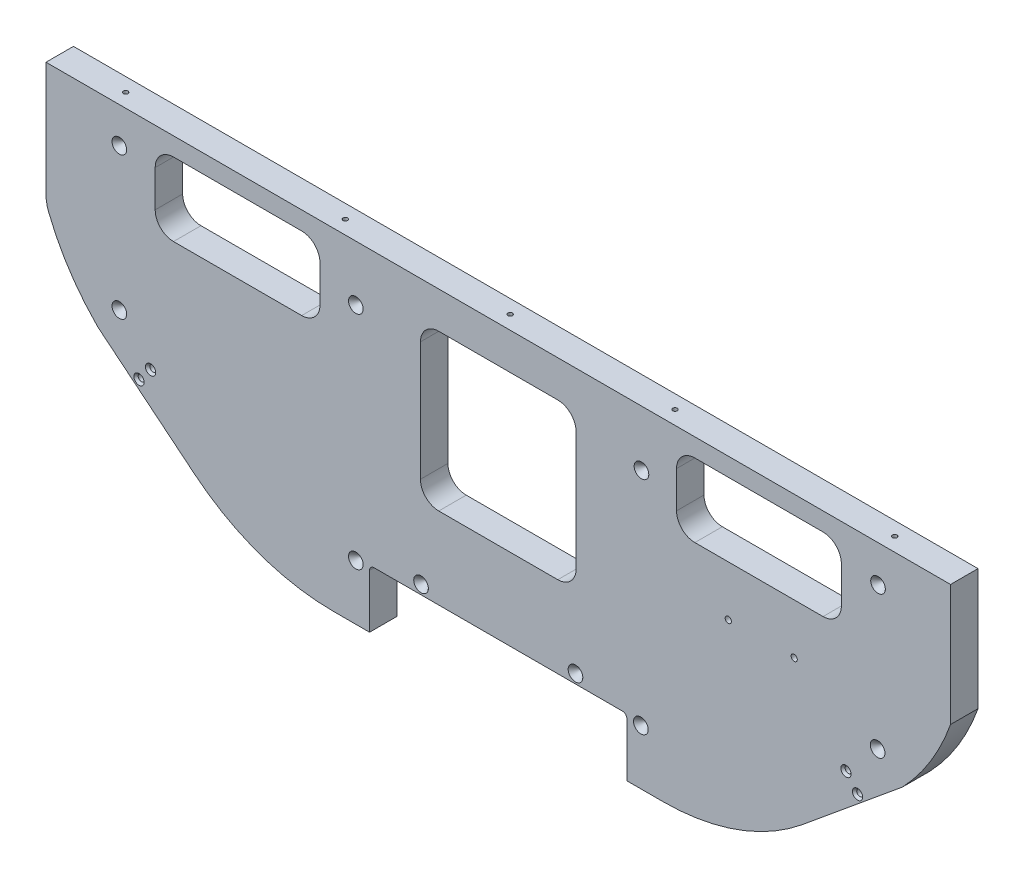
SolidWorks part; units mm, degrees
material "MDF"
ref_plane "Front Plane" through (0, 0, 0) normal (0, 0, 1) x (1, 0, 0)
ref_plane "Top Plane" through (0, 0, 0) normal (0, 1, 0) x (1, 0, 0)
ref_plane "Right Plane" through (0, 0, 0) normal (1, 0, 0) x (0, 0, -1)
sketch "Sketch1" plane through (0, 0, 0) normal (0, 0, 1) x (1, 0, 0)
  line L0 (-394.3667, -87.3125) -> (-394.3667, 23.8125) construction
  line L2 (-618.7884, -233.3625) -> (-593.7567, -233.3625) construction
  line L3 (-394.3667, -87.3125) -> (-394.3667, -3.175)
  line L4 (-497.3744, -199.0142) -> (-427.755, -141.5981)
  line L5 (-708.1202, -233.3625) -> (-593.7567, -233.3625)
  line L6 (-708.1202, -3.175) -> (-708.1202, -233.3625) construction
  line L7 (-1021.7467, -3.175) -> (-394.4938, -3.175) construction
  line L8 (-394.3667, -3.175) -> (-708.1202, -3.175)
  line L9 (-1021.7468, -3.175) -> (-394.4938, -3.175) construction
  line L10 (-976.0267, -152.2395) -> (-918.7391, -199.0142) construction
  line L11 (-1021.7467, -87.3125) -> (-1021.7467, -20.955) construction
  line L12 (-985.5517, -144.4625) -> (-918.7391, -199.0142)
  line L13 (-1021.7467, -87.3125) -> (-1021.7467, -3.175)
  line L14 (-822.3567, -233.3625) -> (-708.1202, -233.3625)
  line L15 (-708.1202, -3.175) -> (-1021.7467, -3.175)
  arc A0 (-427.755, -141.5981) -> (-394.3667, -87.3125) centre (-538.0037, -36.3792) ccw construction
  arc A1 (-593.7567, -233.3625) -> (-497.3744, -199.0142) centre (-593.7567, -80.9625) ccw construction
  arc A2 (-427.755, -141.5981) -> (-394.3667, -87.3125) centre (-538.0037, -36.3792) ccw
  arc A3 (-593.7567, -233.3625) -> (-497.3744, -199.0142) centre (-593.7567, -80.9625) ccw
  arc A4 (-918.7391, -199.0142) -> (-822.3567, -233.3625) centre (-822.3567, -80.9625) ccw construction
  arc A5 (-1021.7467, -87.3125) -> (-985.5517, -144.4625) centre (-878.1098, -36.3792) ccw construction
  arc A6 (-918.7391, -199.0142) -> (-822.3567, -233.3625) centre (-822.3567, -80.9625) ccw
  arc A7 (-1021.7467, -87.3125) -> (-985.5517, -144.4625) centre (-878.1098, -36.3792) ccw
  point P13 (-708.1202, -3.175)
extrude "Boss-Extrude1" add sketch "Sketch1" along normal blind 19.05
hole_wizard "5/64 (0.07813) Diameter Hole1" positions "Sketch2" profile "Sketch3" hole size "5/64" standard "ANSI Inch"
sketch "Sketch2" plane through (-708.0567, 15.875, 6128.5599) normal (0, 1, 0) x (1, 0, 0)
  line L1 (-0.0635, 6109.5099) -> (-0.0635, 6338.7449) construction
  point P0 (-262.8265, 6157.4524)
  point P6 (-98.7933, 6157.4524)
  point P18 (-262.8265, 6233.6524)
  point P19 (-98.7933, 6233.6524)
  point P22 (-262.8265, 6309.8524)
  point P23 (-98.7933, 6309.8524)
  point P24 (-267.97, 6119.0349)
  point P34 (-115.57, 6119.0349)
  point P37 (-1.27, 6119.0349)
  point P40 (113.03, 6119.0349)
  point P44 (265.43, 6119.0349)
  point P55 (98.6663, 6309.8524)
  point P56 (262.6995, 6309.8524)
  point P59 (98.6663, 6233.6524)
  point P60 (262.6995, 6233.6524)
  point P63 (98.6663, 6157.4524)
  point P64 (262.6995, 6157.4524)
sketch "Sketch3" plane through (-970.8832, 15.875, -28.8925) normal (1, 0, 0) x (0, 0, 1)
  line L0 (0, 0) -> (0, 39.0539)
  line L1 (0, 39.0539) -> (1.5875, 38.1)
  line L2 (1.5875, 38.1) -> (1.5875, 4.0177)
  line L3 (1.5875, 4.0177) -> (5.08, 0)
  line L4 (5.08, 0) -> (0, 0)
  line L5 (-1.5875, 4.0177) -> (-5.08, 0) construction
  line L6 (0, 39.0539) -> (-1.5875, 38.1) construction
  line L7 (0, -6.35) -> (0, 107.95) construction
  dimension "Hole Dia." = 3.175
  dimension "Hole Depth" = 38.1
  dimension "Near C'Sink Dia." = 10.16
  dimension "Near C'Sink Angle" = 82
  dimension "Drill Angle" = 118
hole_wizard "5/64 (0.07813) Diameter Hole2" positions "Sketch4" profile "Sketch5" hole size "5/64" standard "ANSI Inch"
sketch "Sketch4" plane through (-708.0567, 1936.854, 19.05) normal (0, 0, 1) x (-1, 0, 0)
  line L23 (262.8265, 2088.1084) -> (262.8265, 2038.7486)
  line L24 (262.8265, 2038.7486) -> (262.8265, 1989.3888)
  line L25 (262.8265, 1989.3888) -> (262.8265, 2038.7486)
  line L26 (262.8265, 2038.7486) -> (262.8265, 1989.3888)
  line L27 (262.8265, 1989.3888) -> (262.8265, 1940.029)
  line L33 (98.7933, 2170.2165) -> (98.7933, 2131.8519)
  line L35 (98.7933, 2131.8519) -> (98.7933, 2093.4873)
  line L36 (98.7933, 2093.4873) -> (98.7933, 2055.1227)
  line L37 (98.7933, 2055.1227) -> (98.7933, 2016.7581)
  line L38 (98.7933, 2016.7581) -> (98.7933, 1978.3935)
  line L39 (98.7933, 1978.3935) -> (98.7933, 1940.029)
  line L44 (89.2683, 2123.544) -> (53.561, 2123.544)
  line L46 (53.561, 2123.544) -> (17.8537, 2123.544)
  line L47 (17.8537, 2123.544) -> (-17.8537, 2123.544)
  line L48 (-17.8537, 2123.544) -> (-53.561, 2123.544)
  line L49 (-53.561, 2123.544) -> (-89.2683, 2123.544)
  line L53 (0, 2170.2165) -> (-0.3175, 1940.029) construction
  line L55 (-99.3221, 1978.6668) -> (-99.4279, 1940.3024)
  line L56 (-99.2163, 2017.0312) -> (-99.3221, 1978.6668)
  line L57 (-99.1104, 2055.3957) -> (-99.2163, 2017.0312)
  line L58 (-99.0046, 2093.7601) -> (-99.1104, 2055.3957)
  line L59 (-98.8988, 2132.1245) -> (-99.0046, 2093.7601)
  line L60 (-98.7929, 2170.489) -> (-98.8988, 2132.1245)
  line L61 (-263.3243, 1990.1145) -> (-263.4605, 1940.7549)
  line L62 (-263.1882, 2039.4741) -> (-263.3243, 1990.1145)
  line L63 (-263.3243, 1990.1145) -> (-263.1882, 2039.4741)
  line L64 (-263.1882, 2039.4741) -> (-263.3243, 1990.1145)
  line L65 (-263.052, 2088.8338) -> (-263.1882, 2039.4741)
  point P71 (262.8265, 1964.7089)
  point P79 (262.8265, 2063.4285)
  point P95 (98.7933, 2131.8519)
  point P103 (98.7933, 1978.3935)
  point P126 (53.561, 2123.544)
  point P134 (-53.561, 2123.544)
  point P162 (-99.3221, 1978.6668)
  point P166 (-98.8988, 2132.1245)
  point P167 (-263.1201, 2064.1539)
  point P169 (-263.3924, 1965.4347)
sketch "Sketch5" plane through (-444.6643, -28.5807, 19.05) normal (1, 0, 0) x (0, -1, 0)
  line L0 (0, 0) -> (0, 38.6962)
  line L1 (0, 38.6962) -> (0.9923, 38.1)
  line L2 (0.9923, 38.1) -> (0.9923, 4.7024)
  line L3 (0.9923, 4.7024) -> (5.08, 0)
  line L4 (5.08, 0) -> (0, 0)
  line L5 (-0.9923, 4.7024) -> (-5.08, 0) construction
  line L6 (0, 38.6962) -> (-0.9923, 38.1) construction
  line L7 (0, -6.35) -> (0, 107.95) construction
  dimension "Hole Dia." = 1.9845
  dimension "Hole Depth" = 38.1
  dimension "Near C'Sink Dia." = 10.16
  dimension "Near C'Sink Angle" = 82
  dimension "Drill Angle" = 118
sketch "Sketch6" plane through (0, 0, 0) normal (0, 0, -1) x (-1, 0, 0)
  line L1 (797.325, -233.3625) -> (618.7884, -233.3625)
  line L2 (797.325, -233.3625) -> (797.325, -193.04)
  line L3 (797.325, -193.04) -> (618.7884, -193.04)
  line L4 (618.7884, -233.3625) -> (618.7884, -193.04)
extrude "Cut-Extrude1" cut sketch "Sketch6" against normal up to next
fillet "Fillet1" radius 25.4 2 edges at (-985.5517, -144.4625, 9.525) (-1021.7467, -87.3125, 9.525)
hole_wizard "#6 Clearance Hole1" positions "Sketch7" profile "Sketch8" hole size "#6" standard "ANSI Inch" end condition up to next
sketch "Sketch7" plane through (0, 0, 19.05) normal (0, 0, 1) x (1, 0, 0)
  arc A0 (-504.7297, -98.0667) -> (-504.7297, -104.8742) centre (-502.7993, -101.4705) ccw construction
  arc A1 (-550.4497, -98.0667) -> (-550.4497, -104.8742) centre (-548.5193, -101.4705) ccw construction
  point P0 (-502.7993, -101.4705)
  point P2 (-548.5193, -101.4705)
sketch "Sketch8" plane through (-502.7993, -101.4705, 19.05) normal (1, 0, 0) x (0, -1, 0)
  line L0 (0, 0) -> (0, 19.05)
  line L1 (0, 19.05) -> (2.1526, 19.05)
  line L2 (2.1526, 19.05) -> (2.1526, 0)
  line L5 (2.1526, 0) -> (0, 0)
  line L11 (0, -6.35) -> (0, 107.95) construction
  dimension "Thru Hole Dia." = 4.3053
  dimension "Thru Hole Depth" = 19.05
hole_wizard "CSK for #6 Flat Head Machine Screw (100)1" positions "Sketch9" profile "Sketch10" countersink size "#6" standard "ANSI Inch" end condition up to next
sketch "Sketch9" plane through (0, 0, 19.05) normal (0, 0, 1) x (1, 0, 0)
  point P0 (-957.2382, -161.4319)
  point P3 (-949.206, -151.5944)
  point P6 (-466.9052, -151.5924)
  point P9 (-458.8731, -161.4298)
sketch "Sketch10" plane through (-957.2382, -161.4319, 19.05) normal (1, 0, 0) x (0, -1, 0)
  line L0 (0, 0) -> (0, 19.05)
  line L1 (0, 19.05) -> (2.1526, 19.05)
  line L2 (2.1526, 19.05) -> (2.1526, 1.5998)
  line L3 (2.1526, 1.5998) -> (3.5433, 0)
  line L5 (3.5433, 0) -> (0, 0)
  line L6 (-2.1526, 1.5998) -> (-3.5433, 0) construction
  line L11 (0, -6.35) -> (0, 107.95) construction
  dimension "Thru Hole Dia." = 4.3053
  dimension "Thru Hole Depth" = 19.05
  dimension "Near C'Sink Dia." = 7.0866
  dimension "Near C'Sink Angle" = 82
sketch "Sketch12" plane through (0, 0, 19.05) normal (0, 0, 1) x (1, 0, 0)
  line L0 (-708.0567, -193.04) -> (-708.0567, -3.175) construction
  line L1 (-797.325, -193.04) -> (-618.7884, -193.04) construction
  line L2 (-394.3667, -3.175) -> (-1021.7467, -3.175) construction
  line L3 (-970.8832, -27.8549) -> (-806.85, -27.8549) construction
  line L4 (-806.85, -41.5396) -> (-806.85, -27.8549) construction
  line L5 (-584.3968, -15.875) -> (-470.0968, -15.875)
  line L6 (-831.7166, -66.675) -> (-946.0166, -66.675)
  line L7 (-831.7166, -66.675) -> (-831.7166, -15.875)
  line L8 (-831.7166, -15.875) -> (-946.0166, -15.875)
  line L9 (-946.0166, -66.675) -> (-946.0166, -15.875)
  line L10 (-831.7166, -66.675) -> (-946.0166, -15.875) construction
  line L11 (-831.7166, -15.875) -> (-946.0166, -66.675) construction
  line L12 (-470.0968, -66.675) -> (-470.0968, -15.875)
  line L13 (-584.3968, -66.675) -> (-470.0968, -66.675)
  line L14 (-584.3968, -66.675) -> (-584.3968, -15.875)
  line L15 (-394.3667, -3.175) -> (-1021.7467, -3.175) construction
  line L16 (-654.0817, -136.525) -> (-762.0317, -136.525)
  line L17 (-654.0817, -136.525) -> (-654.0817, -28.575)
  line L18 (-654.0817, -28.575) -> (-762.0317, -28.575)
  line L19 (-762.0317, -136.525) -> (-762.0317, -28.575)
  line L20 (-654.0817, -136.525) -> (-762.0317, -28.575) construction
  line L21 (-654.0817, -28.575) -> (-762.0317, -136.525) construction
  point P9 (-888.8666, -27.8549)
  point P10 (-888.8666, -41.275)
  point P20 (-708.0567, -82.55)
  dimension "D1" = 114.3
  dimension "D2" = 50.8
  dimension "D3" = 12.7
  dimension "D4" = 107.95
  dimension "D5" = 107.95
  dimension "D6" = 25.4
extrude "Cut-Extrude2" cut sketch "Sketch12" against normal through all
fillet "Fillet2" radius 12.7 12 edges at (-584.3968, -66.675, 9.525) (-584.3968, -15.875, 9.525) (-470.0968, -15.875, 9.525) (-470.0968, -66.675, 9.525) (-654.0817, -136.525, 9.525) (-654.0817, -28.575, 9.525) (-762.0317, -28.575, 9.525) (-762.0317, -136.525, 9.525) (-946.0166, -66.675, 9.525) (-946.0166, -15.875, 9.525) (-831.7166, -15.875, 9.525) (-831.7166, -66.675, 9.525)
fillet "Fillet3" radius 3.175 2 edges at (-618.7884, -193.04, 9.525) (-797.325, -193.04, 9.525)
